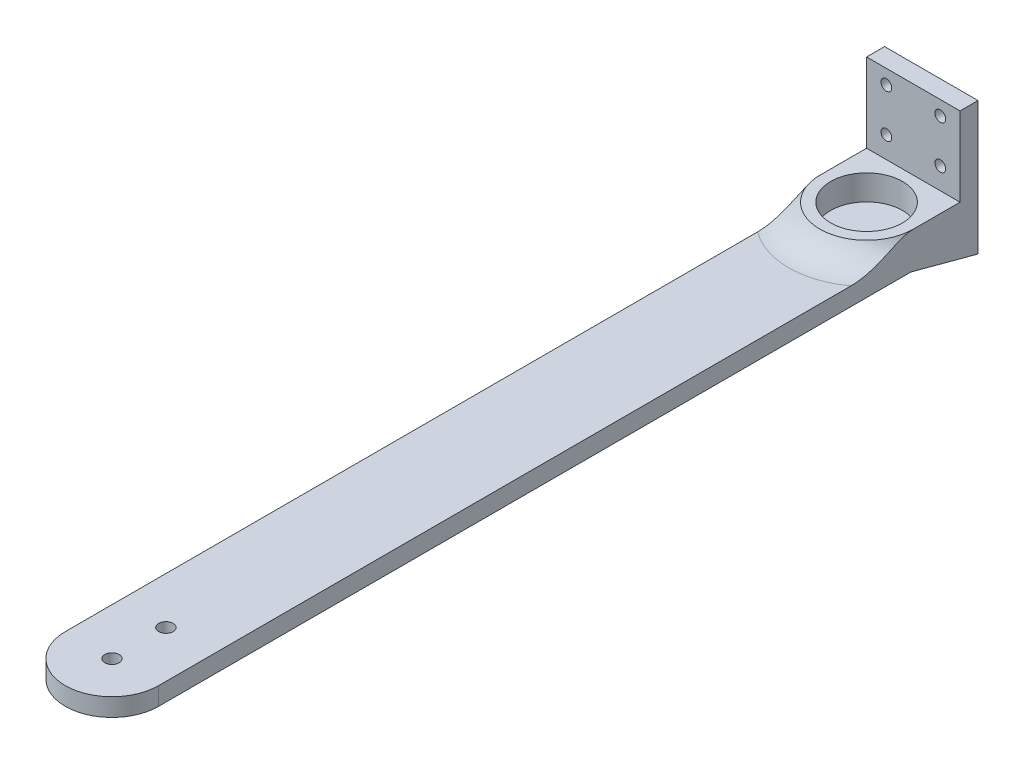
SolidWorks part; units mm, degrees
note: The reader was unsure of these and kept them because the rebuilt part matched: shared geometry of "草图1<3>".
ref_plane "前视基准面" through (0, 0, 0) normal (0, 0, 1) x (1, 0, 0)
ref_plane "上视基准面" through (0, 0, 0) normal (0, 1, 0) x (1, 0, 0)
ref_plane "右视基准面" through (0, 0, 0) normal (1, 0, 0) x (0, 0, -1)
other "Configuration Table"
sketch "草图1" plane through (0, 0, 0) normal (0, 1, 0) x (1, 0, 0)
  line L0 (0, 0) -> (0, -28.1843) construction
  circle A0 centre (0, 0) radius 10
  circle A1 centre (0, 0) radius 13
  dimension "D1" = 20
  dimension "D2" = 26
extrude "凸台-拉伸1" add sketch "草图1" along normal blind 10
extrude "凸台-拉伸2" add sketch "草图1<3>" along normal blind 3
sketch "草图1<3>" plane through (0, 0, 0) normal (0, 1, 0) x (1, 0, 0) same geometry as "草图1"
sketch "草图2" plane through (0, 0, 0) normal (0, -1, 0) x (1, 0, 0)
  line L0 (0, 0) -> (0, 62.3763) construction
  line L1 (-13, 0) -> (-13, 210)
  line L2 (13, 0) -> (13, 210)
  arc A0 (-13, 210) -> (13, 210) centre (0, 210) cw
  circle A1 centre (0, 0) radius 13
  circle A2 centre (0, 0) radius 13
  circle A3 centre (0, 210) radius 2
  circle A4 centre (0, 195) radius 2
  dimension "D4" = 4
  dimension "D2" = 210
  dimension "D3" = 15
  dimension "D1" = 0
extrude "凸台-拉伸3" add sketch "草图2" against normal blind 5
fillet "圆角1" radius 10 1 edges at (0, 5, 13)
ref_plane "基准面1" through (0, 0, -13) normal (0, 0, -1) x (-1, 0, 0)
sketch "草图3" plane through (0, 0, -13) normal (0, 0, -1) x (-1, 0, 0)
  line L0 (0, 0) -> (0, 16) construction
  line L2 (-13, 0) -> (13, 0)
  line L3 (-13, 0) -> (-13, 32)
  line L4 (-13, 32) -> (13, 32)
  line L5 (13, 0) -> (13, 32)
  line L6 (-13, 0) -> (13, 32) construction
  line L7 (-13, 32) -> (13, 0) construction
  dimension "D1" = 32
extrude "凸台-拉伸4" add sketch "草图3" along normal blind 5 separate body
sketch "草图4" plane through (0, 0, -13) normal (0, 0, 1) x (1, 0, 0)
  line L4 (-13, 10) -> (-13, 0)
  line L5 (13, 10) -> (-13, 10)
  line L6 (13, 0) -> (13, 10)
  line L7 (-13, 0) -> (13, 0)
  line L8 (-13, 10) -> (-13, 0)
  line L9 (13, 10) -> (-13, 10)
  line L10 (13, 0) -> (13, 10)
  line L11 (-13, 0) -> (13, 0)
  dimension "D1" = 0
extrude "凸台-拉伸5" add sketch "草图4" along normal up to surface (13 mm away)
sketch "草图5" plane through (-13, 0, 0) normal (-1, 0, 0) x (0, 0, 1)
  line L0 (-18, 0) -> (-18, -5)
  line L1 (-18, -5) -> (0.6603, 0)
  line L2 (-18, 0) -> (210, 0) construction
  line L3 (-18, 0) -> (0.6603, 0)
  dimension "D1" = 5
  dimension "D2" = 15
extrude "凸台-拉伸6" add sketch "草图5" against normal up to surface (26 mm away) up to face at (13, 11.941, 46.3488)
sketch "草图6" plane through (0, 0, -13) normal (0, 0, 1) x (1, 0, 0)
  line L0 (0, 0) -> (0, 22) construction
  line L1 (-13, 32) -> (13, 32) construction
  line L2 (-7.5, 16) -> (7.5, 16) construction
  line L3 (-7.5, 16) -> (-7.5, 28) construction
  line L4 (-7.5, 28) -> (7.5, 28) construction
  line L5 (7.5, 16) -> (7.5, 28) construction
  line L6 (-7.5, 16) -> (7.5, 28) construction
  line L7 (-7.5, 28) -> (7.5, 16) construction
  circle A0 centre (-7.5, 28) radius 1.5
  circle A1 centre (7.5, 28) radius 1.5
  circle A2 centre (7.5, 16) radius 1.5
  circle A3 centre (-7.5, 16) radius 1.5
  dimension "D4" = 3
  dimension "D1" = 15
  dimension "D2" = 12
  dimension "D3" = 10
extrude "切除-拉伸1" cut sketch "草图6" against normal through all
